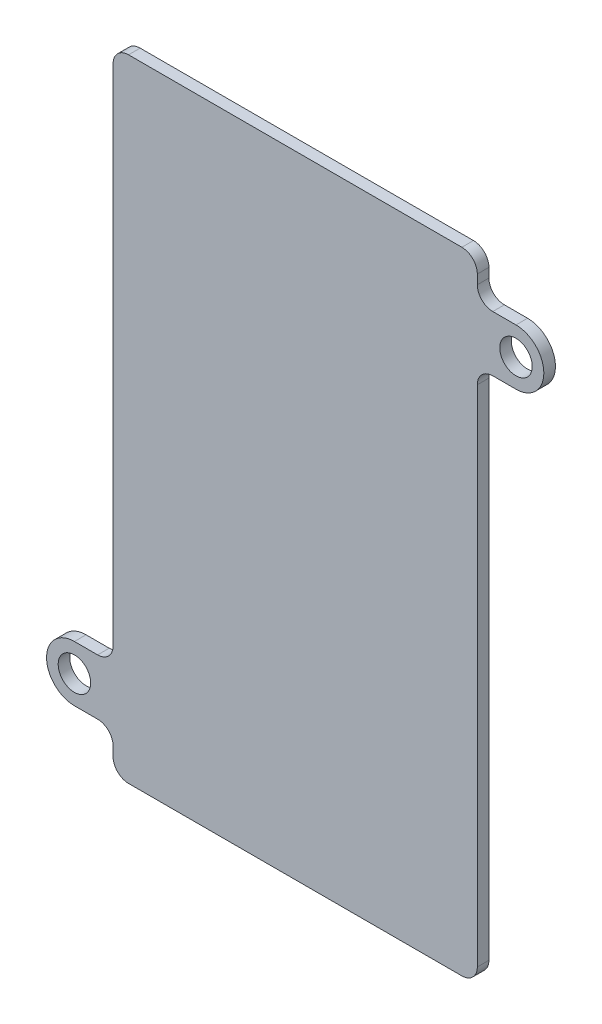
SolidWorks part; units mm, degrees
ref_plane "Front Plane" through (0, 0, 0) normal (0, 0, 1) x (1, 0, 0)
ref_plane "Top Plane" through (0, 0, 0) normal (0, 1, 0) x (1, 0, 0)
ref_plane "Right Plane" through (0, 0, 0) normal (1, 0, 0) x (0, 0, -1)
sketch "Sketch1" plane through (0, 0, 0) normal (0, 0, -1) x (-1, 0, 0)
  line L0 (-23.55, 40.8) -> (23.55, 40.8)
  line L5 (23.55, -40.8) -> (23.55, 40.8)
  line L6 (-23.55, -40.8) -> (23.55, -40.8)
  line L11 (-23.55, -40.8) -> (-23.55, 40.8)
  line L12 (-28.55, 32) -> (28.55, -32) construction
  line L13 (-28.55, 35.6) -> (-23.55, 35.6)
  line L14 (-20.55, -37.8) -> (20.55, -37.8)
  line L15 (-20.55, -37.8) -> (-20.55, 37.8)
  line L16 (-20.55, 37.8) -> (20.55, 37.8)
  line L17 (20.55, -37.8) -> (20.55, 37.8)
  line L18 (-20.55, -37.8) -> (20.55, 37.8) construction
  line L19 (-20.55, 37.8) -> (20.55, -37.8) construction
  line L20 (-28.55, 28.4) -> (-23.55, 28.4)
  line L21 (28.55, -35.6) -> (23.55, -35.6)
  line L22 (28.55, -28.4) -> (23.55, -28.4)
  line L24 (-5, 40.8) -> (5, 40.8)
  line L25 (-5, 40.8) -> (-5, 37.8)
  line L26 (-5, 37.8) -> (5, 37.8)
  line L27 (5, 40.8) -> (5, 37.8)
  circle A0 centre (28.55, -32) radius 2.1
  circle A1 centre (-28.55, 32) radius 2.1
  circle A2 centre (-28.55, 32) radius 3.6
  circle A3 centre (28.55, -32) radius 3.6
  point P0 (0, 0)
  point P11 (0, 0)
  point P25 (0, 37.8)
  dimension "D5" = 1.5
  dimension "D6" = 4.2
  dimension "D2" = 3
  dimension "D3" = 41.1
  dimension "D4" = 75.6
  dimension "D7" = 32
  dimension "D8" = 5
  dimension "D9" = 10
extrude "Boss-Extrude1" add sketch "Sketch1" along normal blind 1.5 contours L22 A3 L21 L5 | L27 L0 L5 L6 L11 L25 L16 L15 L14 L17 | A2 A1 | L20 A2 L13 L11 | L17 L14 L15 L16 | L0 L27 L16 L25 | A3 | A0 region at (14.275, 39.8578, 0) region at (0, 39.3, 0) region at (24.7849, 32, 0) region at (0, 0, 0) region at (26.0764, 34.4736, 0) region at (-24.7849, -32, 0)
fillet "Fillet1" radius 2 8 edges at (23.55, 28.4, -0.75) (-23.55, -28.4, -0.75) (23.55, 35.6, -0.75) (23.55, 40.8, -0.75) (-23.55, 40.8, -0.75) (23.55, -40.8, -0.75) (-23.55, -40.8, -0.75) (-23.55, -35.6, -0.75)
